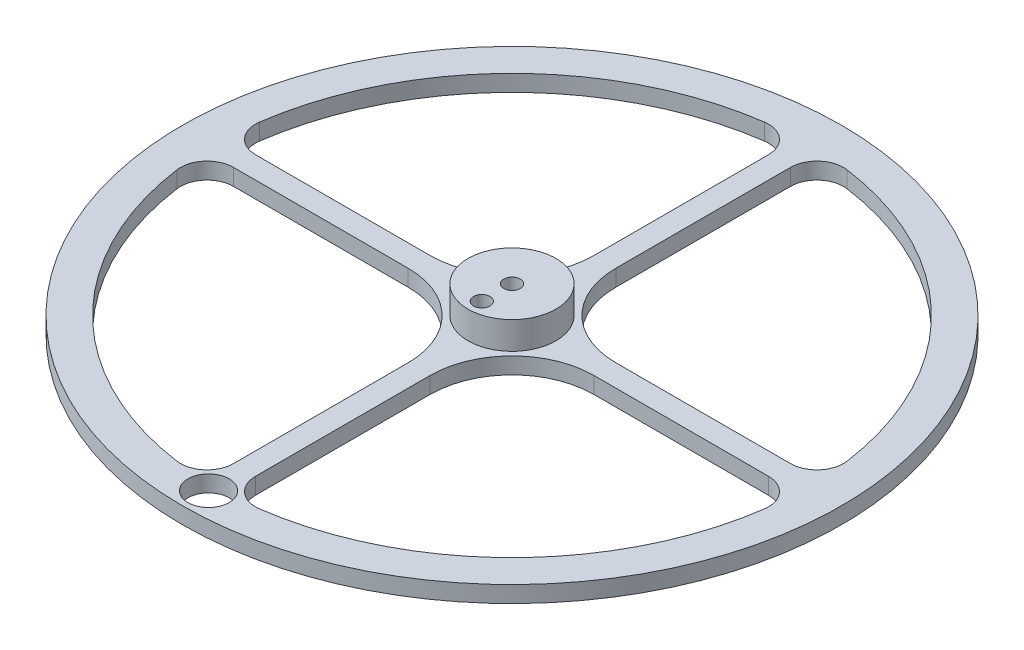
SolidWorks part; units mm, degrees
ref_plane "Front Plane" through (0, 0, 0) normal (0, 0, 1) x (1, 0, 0)
ref_plane "Top Plane" through (0, 0, 0) normal (0, 1, 0) x (1, 0, 0)
ref_plane "Right Plane" through (0, 0, 0) normal (1, 0, 0) x (0, 0, -1)
sketch "Sketch1" plane through (0, 0, 0) normal (0, 1, 0) x (1, 0, 0)
  line L0 (2, -48.6942) -> (2, -16.8995)
  line L1 (0, 0) -> (-6.364, -6.364) construction
  line L2 (0, 0) -> (6.364, -6.364) construction
  line L3 (-2, -16.8995) -> (-2, -48.6942)
  line L4 (-2, -16.8995) -> (2, -16.8995) construction
  line L5 (0, -9) -> (0, 9) construction
  line L6 (0, -60) -> (0, 9) construction
  line L7 (-16.8995, 2) -> (-48.6942, 2)
  line L8 (-48.6942, -2) -> (-16.8995, -2)
  line L9 (-11.0325, 9) -> (11.0325, 9) construction
  line L10 (0, 9) -> (0, 10.9405) construction
  line L11 (2, 16.8995) -> (2, 48.6942)
  line L12 (0, -16.8995) -> (0, -9) construction
  line L13 (-7.5, -53.4766) -> (7.5, -53.4766) construction
  line L14 (0, -60) -> (0, -53.4766) construction
  line L15 (-2, 48.6942) -> (-2, 16.8995)
  line L16 (16.8995, -2) -> (48.6942, -2)
  line L17 (48.6942, 2) -> (16.8995, 2)
  circle A0 centre (0, 0) radius 60
  circle A1 centre (0, 0) radius 54
  circle A2 centre (0, 0) radius 8
  circle A3 centre (0, 0) radius 9 construction
  arc A4 (-2, -16.8995) -> (-6.364, -6.364) centre (-16.8995, -16.8995) ccw
  arc A5 (-2, -48.6942) -> (-7.5, -53.4766) centre (-6.8293, -48.6942) cw
  arc A6 (2, -48.6942) -> (7.5, -53.4766) centre (6.8293, -48.6942) ccw
  arc A7 (2, -16.8995) -> (6.364, -6.364) centre (16.8995, -16.8995) cw
  arc A8 (-16.8995, 2) -> (-6.364, 6.364) centre (-16.8995, 16.8995) ccw
  arc A9 (-16.8995, -2) -> (-6.364, -6.364) centre (-16.8995, -16.8995) cw
  arc A10 (-48.6942, 2) -> (-53.4766, 7.5) centre (-48.6942, 6.8293) cw
  arc A11 (-48.6942, -2) -> (-53.4766, -7.5) centre (-48.6942, -6.8293) ccw
  arc A12 (2, 16.8995) -> (6.364, 6.364) centre (16.8995, 16.8995) ccw
  arc A13 (-2, 16.8995) -> (-6.364, 6.364) centre (-16.8995, 16.8995) cw
  arc A14 (2, 48.6942) -> (7.5, 53.4766) centre (6.8293, 48.6942) cw
  arc A17 (-2, 48.6942) -> (-7.5, 53.4766) centre (-6.8293, 48.6942) ccw
  arc A18 (16.8995, -2) -> (6.364, -6.364) centre (16.8995, -16.8995) ccw
  arc A19 (16.8995, 2) -> (6.364, 6.364) centre (16.8995, 16.8995) cw
  arc A20 (48.6942, -2) -> (53.4766, -7.5) centre (48.6942, -6.8293) cw
  arc A21 (48.6942, 2) -> (53.4766, 7.5) centre (48.6942, 6.8293) ccw
  point P71 (0, 0)
  dimension "D1" = 6
  dimension "D5" = 16
  dimension "D9" = 120
  dimension "D2" = 69
  dimension "D3" = 45
  dimension "D4" = 4
  dimension "D7" = 4
  dimension "D10" = 15
extrude "Boss-Extrude1" add sketch "Sketch1" against normal blind 3 contours A0 A1 | L3 A5 A1 A6 L0 A2 | A2 region at (2.6583, 0, 53.491) region at (-58.3029, 0, 0) region at (0, 0, 0)
extrude "Boss-Extrude2" add sketch "Sketch1<3>" along normal blind 5 contours A2 region at (0, 0, 0)
sketch "Sketch1<3>" plane through (0, 0, 0) normal (0, 1, 0) x (1, 0, 0) same geometry as "Sketch1"
sketch "Sketch2" plane through (0, 5, 0) normal (0, 1, 0) x (1, 0, 0)
  circle A0 centre (0, 0) radius 1.5
  dimension "D1" = 3
extrude "Cut-Extrude1" cut sketch "Sketch2" against normal up to next
sketch "Sketch3" plane through (0, 0, 0) normal (0, 1, 0) x (1, 0, 0)
  line L0 (0, 0) -> (0, -55.25) construction
  circle A0 centre (0, -55.25) radius 3.75
  dimension "D1" = 7.5
  dimension "D2" = 55.25
extrude "Cut-Extrude2" cut sketch "Sketch3" against normal up to next
sketch "Sketch4" plane through (0, 5, 0) normal (0, 1, 0) x (1, 0, 0)
  line L0 (0, 0) -> (0, -5.5) construction
  circle A0 centre (0, -5.5) radius 1.5
  dimension "D2" = 3
  dimension "D1" = 5.5
extrude "Cut-Extrude3" cut sketch "Sketch4" against normal up to surface (5 mm away) up to face at (0, 0, 59)
